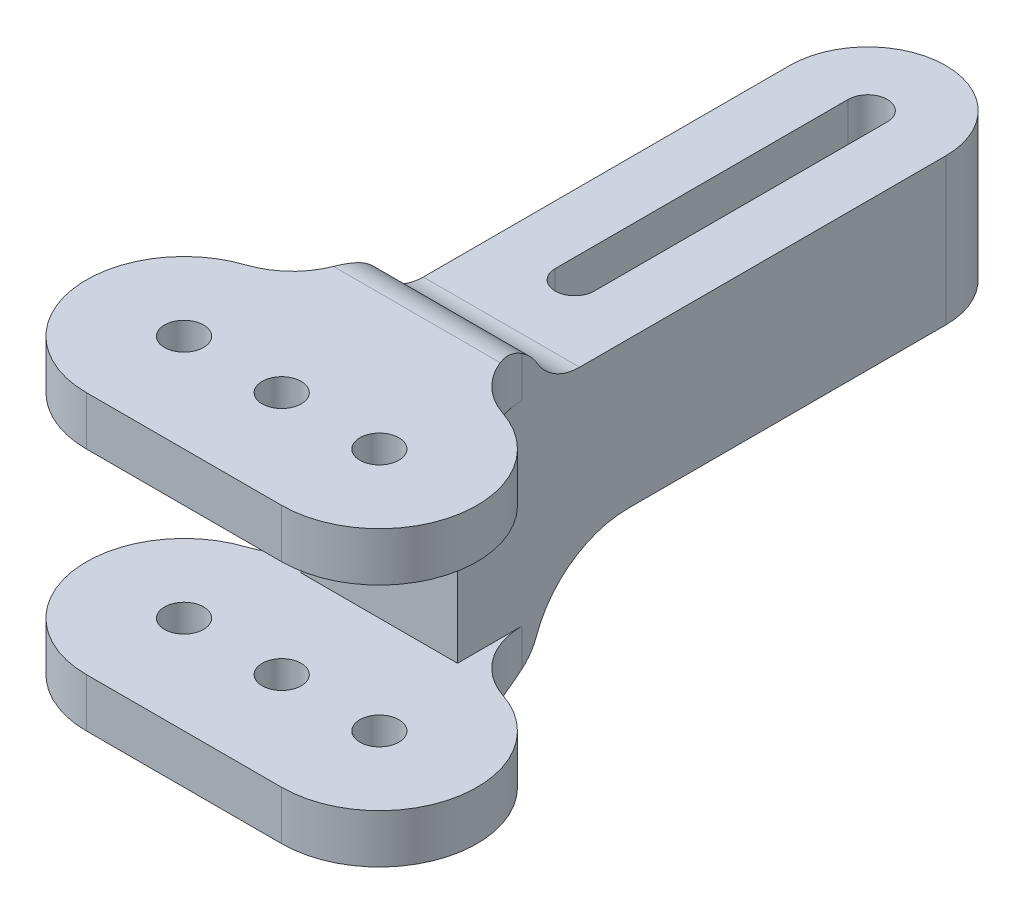
SolidWorks part; units mm, degrees
ref_plane "Front Plane" through (0, 0, 0) normal (0, 0, 1) x (1, 0, 0)
ref_plane "Top Plane" through (0, 0, 0) normal (0, 1, 0) x (1, 0, 0)
ref_plane "Right Plane" through (0, 0, 0) normal (1, 0, 0) x (0, 0, -1)
sketch "Sketch1" plane through (0, 0, 0) normal (0, 1, 0) x (1, 0, 0)
  line L0 (0, 0) -> (0, -30) construction
  line L1 (2, 0) -> (2, -30)
  line L2 (-2, 0) -> (-2, -30)
  line L3 (-8, 0) -> (-8, -50)
  line L4 (-8, -50) -> (8, -50)
  line L5 (8, -50) -> (8, 0)
  circle A0 centre (0, 0) radius 8
  arc A1 (2, 0) -> (-2, 0) centre (0, 0) ccw
  arc A2 (-2, -30) -> (2, -30) centre (0, -30) ccw
  point P3 (0, -15)
  dimension "D1" = 2
  dimension "D2" = 6
  dimension "D3" = 30
  dimension "D4" = 50
extrude "Boss-Extrude1" add sketch "Sketch1" along normal blind 15 contours A1 L1 A0 L2 | A2 L2 A0 L3 L4 L5 L1 region at (0, 0, -2.2245) region at (6.7396, 0, 5.2205)
sketch "Sketch3" plane through (0, 15, 0) normal (0, 1, 0) x (1, 0, 0)
  line L0 (8, -50) -> (8, 0) construction
  line L1 (-8, -50) -> (8, -50) construction
  line L2 (-8, -50) -> (-8, -70) construction
  line L3 (-8, -70) -> (8, -70)
  line L4 (8, -50) -> (8, -70) construction
  line L5 (-10, -70) -> (-8, -70)
  line L6 (-8, -50) -> (8, -50) construction
  line L7 (-8, -50) -> (-8, -42.5)
  line L8 (-8, -42.5) -> (8, -42.5)
  line L9 (8, -50) -> (8, -42.5)
  line L10 (0, -70) -> (0, -42.5) construction
  line L12 (31, -60) -> (-25.0026, -60) construction
  line L13 (10, -50) -> (8, -50)
  line L14 (10, -70) -> (8, -70)
  line L15 (-8, -50) -> (-10, -50)
  arc A2 (10, -50) -> (10, -70) centre (10, -60) cw
  circle A5 centre (-10, -60) radius 2
  circle A6 centre (0, -60) radius 2
  circle A7 centre (10, -60) radius 2
  arc A8 (-10, -50) -> (-10, -70) centre (-10, -60) ccw
  dimension "D3" = 10
  dimension "D5" = 4
  dimension "D6" = 10
  dimension "D7" = 10
  dimension "D1" = 20
  dimension "D2" = 7.5
extrude "Boss-Extrude2" add sketch "Sketch3" along normal blind 5
fillet "Fillet3" radius 5 1 edges at (0, 15, 42.5)
fillet "Fillet4" radius 5 1 edges at (0, 20, 42.5)
fillet "Fillet5" radius 7.5 2 edges at (8, 17.5, 50) (-8, 17.5, 50)
sketch "Sketch7" plane through (0, 0, 0) normal (0, -1, 0) x (1, 0, 0)
  line L4 (-8, 43.3868) -> (-8, 50)
  line L5 (-8, 50) -> (8, 50)
  line L6 (8, 50) -> (8, 43.3868)
  line L7 (10, 70) -> (-10, 70)
  line L8 (-8, 43.3868) -> (-8, 50)
  line L9 (-8, 50) -> (8, 50)
  line L10 (8, 50) -> (8, 43.3868)
  line L11 (10, 70) -> (-10, 70)
  arc A4 (-10, 70) -> (-13.1429, 50.5067) centre (-10, 60) ccw
  arc A5 (-8, 43.3868) -> (-13.1429, 50.5067) centre (-15.5, 43.3868) ccw
  arc A6 (13.1429, 50.5067) -> (8, 43.3868) centre (15.5, 43.3868) ccw
  arc A7 (13.1429, 50.5067) -> (10, 70) centre (10, 60) ccw
  arc A8 (-10, 70) -> (-13.1429, 50.5067) centre (-10, 60) ccw
  arc A9 (-8, 43.3868) -> (-13.1429, 50.5067) centre (-15.5, 43.3868) ccw
  arc A10 (13.1429, 50.5067) -> (8, 43.3868) centre (15.5, 43.3868) ccw
  arc A11 (13.1429, 50.5067) -> (10, 70) centre (10, 60) ccw
  dimension "D1" = 0
extrude "Boss-Extrude4" add sketch "Sketch7" along normal blind 5 from offset 5 separate body
sketch "Sketch8" plane through (0, 0, 0) normal (0, -1, 0) x (1, 0, 0)
  line L0 (8, 50) -> (8, 0) construction
  line L1 (-8, 50) -> (8, 50)
  line L2 (-8, 50) -> (-8, 42.5)
  line L3 (-8, 42.5) -> (8, 42.5)
  line L4 (8, 50) -> (8, 42.5)
  dimension "D1" = 7.5
extrude "Boss-Extrude5" add sketch "Sketch8" along normal up to surface (10 mm away) up to face at (0, -10, 54.0159)
fillet "Fillet6" radius 10 1 edges at (0, 0, 42.5)
fillet "Fillet7" radius 5 1 edges at (0, -10, 42.5)
sketch "Sketch9" plane through (0, -5, 0) normal (0, 1, 0) x (1, 0, 0)
  circle A0 centre (-10, -60) radius 2 construction
  circle A1 centre (0, -60) radius 2 construction
  circle A2 centre (10, -60) radius 2 construction
  circle A3 centre (-10, -60) radius 2
  circle A4 centre (0, -60) radius 2
  circle A5 centre (10, -60) radius 2
extrude "Cut-Extrude1" cut sketch "Sketch9" against normal blind 5
